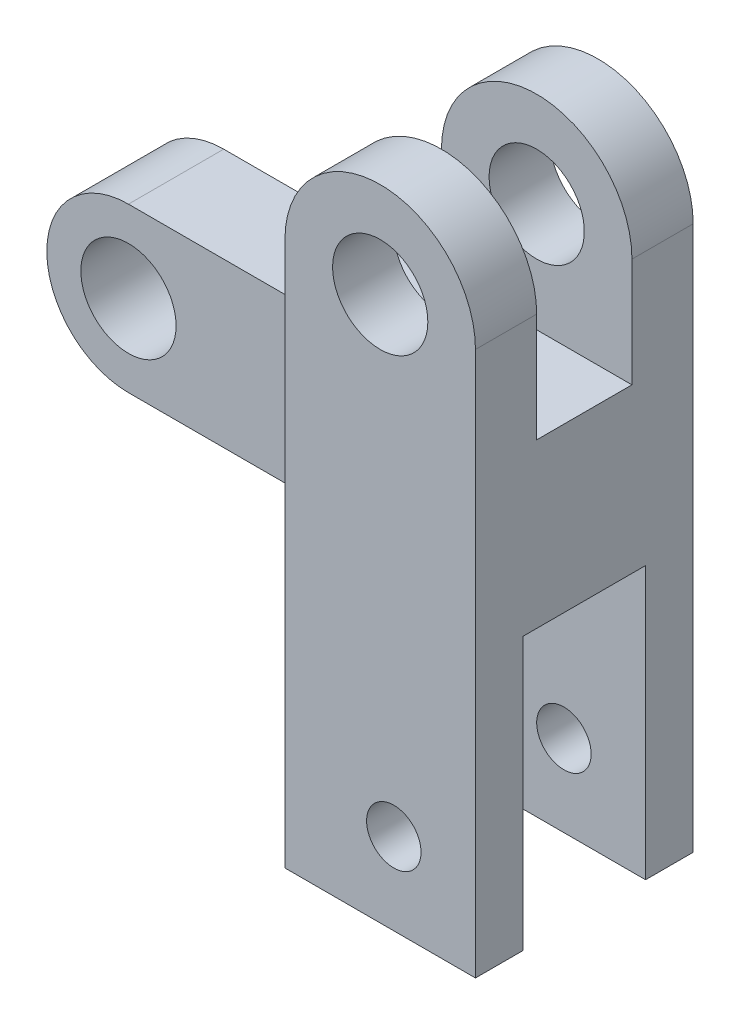
SolidWorks part; units mm, degrees
ref_plane "前视基准面" through (0, 0, 0) normal (0, 0, 1) x (1, 0, 0)
ref_plane "上视基准面" through (0, 0, 0) normal (0, 1, 0) x (1, 0, 0)
ref_plane "右视基准面" through (0, 0, 0) normal (1, 0, 0) x (0, 0, -1)
other "Configuration Table"
sketch "草图1" plane through (0, 0, 0) normal (0, 1, 0) x (1, 0, 0)
  line L1 (0, 3.5) -> (7, 3.5)
  line L2 (0, -3.5) -> (7, -3.5)
  line L3 (0, 3.5) -> (7, 3.5) construction
  line L4 (7, 3.5) -> (7, -3.5)
  line L5 (0, 3.5) -> (0, -3.5)
  dimension "D1" = 7
  dimension "D4" = 90
  dimension "D5" = 7
extrude "凸台-拉伸1" add sketch "草图1" along normal blind 2.4
sketch "草图10" plane through (0, 0, -3.5) normal (0, 0, -1) x (-1, 0, 0)
  line L3 (-7, 2.4) -> (0, 2.4) construction
  line L6 (-7, 2.4) -> (0, 2.4)
  line L7 (0, 2.4) -> (0, 13)
  line L9 (-7, 13) -> (-7, 2.4)
  line L10 (0, 2.4) -> (0, 0) construction
  arc A1 (0, 13) -> (-7, 13) centre (-3.5, 13) ccw
  line M3 (0, 2.4) -> (-7, 2.4)
  dimension "D8" = 3.5
  dimension "D9" = 13
extrude "凸台-拉伸6" add sketch "草图10" against normal blind 1.75 contours L7 A1 L9 M3 region at (3.5, 9.0973, -3.5)
extrude "凸台-拉伸8" add sketch "草图10<2>" along normal blind 1.75 from offset 7 contours L7 A1 L9 M3 region at (3.5, 9.0973, -3.5) offset against normal yes
sketch "草图10<2>" plane through (0, 0, -3.5) normal (0, 0, -1) x (-1, 0, 0) same geometry as "草图10"
sketch "草图11" plane through (0, 0, -3.5) normal (0, 0, -1) x (-1, 0, 0)
  circle A2 centre (-3.5, 13) radius 1.75
  dimension "D3" = 3.5
extrude "切除-拉伸1" cut sketch "草图11" against normal through all
sketch "草图17" plane through (0, 0, 0) normal (0, -1, 0) x (1, 0, 0)
  line L6 (0, 3.5) -> (0, -3.5)
  line L7 (0, -3.5) -> (7, -3.5)
  line L8 (7, -3.5) -> (7, 3.5)
  line L9 (7, 3.5) -> (0, 3.5)
  line L12 (0, 3.5) -> (0, -3.5)
  line L13 (0, -3.5) -> (7, -3.5)
  line L14 (7, -3.5) -> (7, 3.5)
  line L15 (7, 3.5) -> (0, 3.5)
  dimension "D1" = 0
extrude "凸台-拉伸10" add sketch "草图17" along normal blind 7
sketch "草图15" plane through (0, 0, 0) normal (0, 0, 1) x (1, 0, 0)
  line L2 (7, 9) -> (7, 3)
  line L10 (7, 13) -> (7, -7) construction
  line L14 (-8, 9) -> (7, 9)
  line L15 (7, 13) -> (7, -7) construction
  line L17 (7, 2.4) -> (7.3779, 2.4)
  line L18 (0, 2.4) -> (7, 2.4) construction
  line L19 (-8, 3) -> (7, 3)
  line L20 (7, -7) -> (0, -7) construction
  arc A0 (-8, 3) -> (-8, 9) centre (-8, 6) cw
  circle A1 centre (-8, 6) radius 1.75
  dimension "D3" = 3.5
  dimension "D1" = 3
  dimension "D2" = 10
  dimension "D4" = 15
extrude "凸台-拉伸9" add sketch "草图15" along normal mid plane 3.5 contours A0 L19 L2 L14 A1 region at (-1.0488, 6, 0)
sketch "草图12" plane through (0, 4, 3.5) normal (0, 0, -1) x (1, 0, 0)
  line L0 (0, 11) -> (7, 11) construction
  line L2 (7, -9) -> (7, 11) construction
  circle A0 centre (4, 8) radius 1
  dimension "D2" = 2
  dimension "D1" = 3
  dimension "D3" = 3
extrude "切除-拉伸2" cut sketch "草图12" along normal through all
sketch "草图18" plane through (7.4, -7, 0) normal (0, 1, 0) x (1, 0, 0)
  line L0 (-0.4, 1.75) -> (-0.4, 3.5) construction
  line L11 (-7.4, -2.25) -> (-0.4, -2.25)
  line L12 (-7.4, -2.25) -> (-7.4, 2.25)
  line L13 (-7.4, 2.25) -> (-0.4, 2.25)
  line L14 (-0.4, -2.25) -> (-0.4, 2.25)
  point P4 (-7.4, 0)
  dimension "D1" = 4.5
  dimension "D2" = 7
extrude "切除-拉伸4" cut sketch "草图18" along normal blind 10
sketch "草图19" plane through (0, 0, 3.5) normal (0, 0, 1) x (1, 0, 0)
  line L4 (0, 13) -> (0, -7)
  line L5 (0, -7) -> (7, -7)
  line L6 (7, -7) -> (7, 13)
  line L8 (0, 13) -> (0, -7)
  line L9 (0, -7) -> (7, -7)
  line L10 (7, -7) -> (7, 13)
  circle A0 centre (4, -4) radius 1 construction
  circle A1 centre (4, -4) radius 1
  circle A2 centre (3.5, 13) radius 1.75 construction
  arc A3 (7, 13) -> (0, 13) centre (3.5, 13) ccw
  arc A4 (7, 13) -> (0, 13) centre (3.5, 13) ccw
  circle A5 centre (3.5, 13) radius 1.75
  dimension "D1" = 0
extrude "凸台-拉伸11" add sketch "草图19" along normal blind 0.5
sketch "草图20" plane through (0, 0, -3.5) normal (0, 0, -1) x (-1, 0, 0)
  line L4 (-7, 13) -> (-7, -7)
  line L5 (-7, -7) -> (0, -7)
  line L6 (0, -7) -> (0, 13)
  line L8 (-7, 13) -> (-7, -7)
  line L9 (-7, -7) -> (0, -7)
  line L10 (0, -7) -> (0, 13)
  circle A0 centre (-4, -4) radius 1 construction
  circle A1 centre (-4, -4) radius 1
  circle A2 centre (-3.5, 13) radius 1.75 construction
  arc A3 (0, 13) -> (-7, 13) centre (-3.5, 13) ccw
  arc A4 (0, 13) -> (-7, 13) centre (-3.5, 13) ccw
  circle A5 centre (-3.5, 13) radius 1.75
  dimension "D1" = 0
extrude "凸台-拉伸12" add sketch "草图20" along normal blind 0.5
